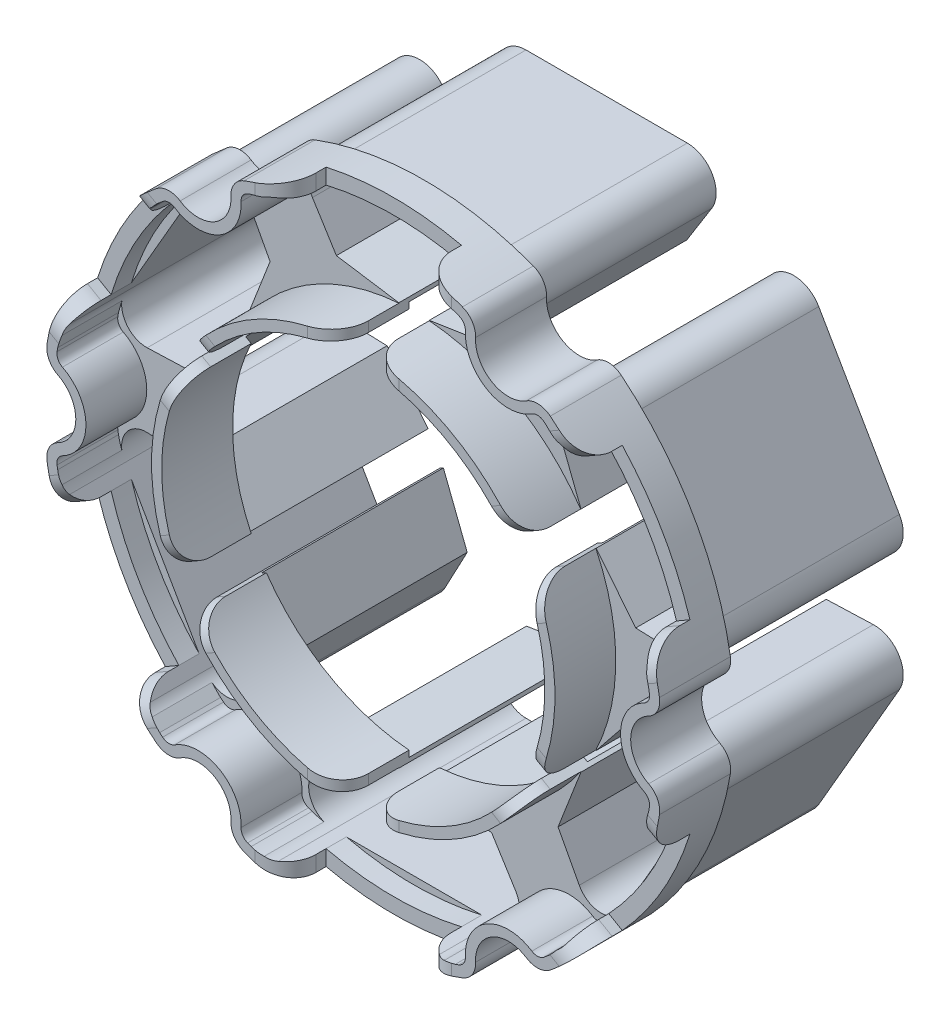
SolidWorks part; units mm, degrees
ref_plane "Ön Düzlem" through (0, 0, 0) normal (0, 0, 1) x (1, 0, 0)
ref_plane "Üst Düzlem" through (0, 0, 0) normal (0, 1, 0) x (1, 0, 0)
ref_plane "Sağ Düzlem" through (0, 0, 0) normal (1, 0, 0) x (0, 0, -1)
sketch "Çizim2" plane through (0, 0, 0) normal (0, 0, 1) x (1, 0, 0)
  line L0 (-1.5, 18.3137) -> (-1.5, 19.3137) construction
  line L13 (1.5, 18.3137) -> (1.5, 19.3137) construction
  line L14 (1.5, 19.3137) -> (8, 20.3137) construction
  line L15 (-1.5, 19.3137) -> (-8, 20.3137) construction
  line L16 (8, 20.3137) -> (10.5, 24.3137) construction
  line L17 (-8, 20.3137) -> (-10.5, 24.3137) construction
  line L18 (-7.956, 28.9037) -> (7.956, 28.9037) construction
  line L20 (-1.5, 19.4654) -> (-7.9092, 20.4515)
  line L21 (-7.9092, 20.4515) -> (-10.3728, 24.3932)
  line L22 (-7.956, 28.7537) -> (7.956, 28.7537)
  line L23 (7.9092, 20.4515) -> (10.3728, 24.3932)
  line L24 (1.5, 19.4654) -> (7.9092, 20.4515)
  line L27 (1.5, 19.8803) -> (7.6612, 20.8281)
  line L28 (7.6612, 20.8281) -> (10.0251, 24.6105)
  line L29 (-7.956, 28.3437) -> (7.956, 28.3437)
  line L30 (-7.6612, 20.8281) -> (-10.0251, 24.6105)
  line L31 (-1.5, 19.8803) -> (-7.6612, 20.8281)
  line L120 (-0.94, 18.3137) -> (-0.94, 19.7941) construction
  line L121 (-1.35, 18.3137) -> (-1.35, 19.4424) construction
  line L122 (1.35, 18.3137) -> (1.35, 19.4424) construction
  line L123 (0.94, 18.3137) -> (0.94, 19.7941) construction
  line L133 (-0.94, 19.7941) -> (-7.6612, 20.8281) construction
  line L134 (0.94, 19.7941) -> (7.6612, 20.8281) construction
  line L145 (-1.5, 19.8803) -> (-1.5, 19.4654)
  line L146 (1.5, 19.8803) -> (1.5, 19.4654)
  line L147 (17.8718, 8.7595) -> (21.8683, 3.7793) [skipped]
  line L148 (21.8683, 3.7793) -> (26.3259, 3.6232) [skipped]
  line L149 (20.5683, 21.0619) -> (28.5243, 7.2817) [skipped]
  line L150 (14.2071, 17.0488) -> (16.3007, 20.9872) [skipped]
  line L151 (16.5218, 11.0977) -> (14.2071, 17.0488) [skipped]
  line L152 (-1.35, 19.4424) -> (-7.9092, 20.4515) construction
  line L153 (16.1626, 10.8903) -> (13.7569, 17.0753) [skipped]
  line L154 (13.7569, 17.0753) -> (15.9387, 21.1797) [skipped]
  line L155 (20.9234, 21.2669) -> (28.8794, 7.4867) [skipped]
  line L156 (21.6661, 3.3761) -> (26.3115, 3.2135) [skipped]
  line L157 (17.5126, 8.552) -> (21.6661, 3.3761) [skipped]
  line L158 (1.35, 19.4424) -> (7.9092, 20.4515) construction
  line L159 (-17.8718, 8.7595) -> (-21.8683, 3.7793) [skipped]
  line L160 (-21.8683, 3.7793) -> (-26.3259, 3.6232) [skipped]
  line L161 (-28.5243, 7.2817) -> (-20.5683, 21.0619) [skipped]
  line L162 (-14.2071, 17.0488) -> (-16.3007, 20.9872) [skipped]
  line L163 (-16.5218, 11.0977) -> (-14.2071, 17.0488) [skipped]
  line L164 (16.4668, 11.2392) -> (14.2071, 17.0488)
  line L165 (-16.1626, 10.8903) -> (-13.7569, 17.0753) [skipped]
  line L166 (-13.7569, 17.0753) -> (-15.9387, 21.1797) [skipped]
  line L167 (-28.8794, 7.4867) -> (-20.9234, 21.2669) [skipped]
  line L168 (-21.6661, 3.3761) -> (-26.3115, 3.2135) [skipped]
  line L169 (-17.5126, 8.552) -> (-21.6661, 3.3761) [skipped]
  line L170 (14.2071, 17.0488) -> (16.3007, 20.9872)
  line L171 (17.5126, -8.552) -> (21.6661, -3.3761) [skipped]
  line L172 (21.6661, -3.3761) -> (26.3115, -3.2135) [skipped]
  line L173 (28.8794, -7.4867) -> (20.9234, -21.2669) [skipped]
  line L174 (13.7569, -17.0753) -> (15.9387, -21.1797) [skipped]
  line L175 (16.1626, -10.8903) -> (13.7569, -17.0753) [skipped]
  line L176 (20.5683, 21.0619) -> (28.5243, 7.2817)
  line L177 (16.5218, -11.0977) -> (14.2071, -17.0488) [skipped]
  line L178 (14.2071, -17.0488) -> (16.3007, -20.9872) [skipped]
  line L179 (28.5243, -7.2817) -> (20.5683, -21.0619) [skipped]
  line L180 (21.8683, -3.7793) -> (26.3259, -3.6232) [skipped]
  line L181 (17.8718, -8.7595) -> (21.8683, -3.7793) [skipped]
  line L182 (21.8683, 3.7793) -> (26.3259, 3.6232)
  line L183 (1.35, -19.4424) -> (7.9092, -20.4515) [skipped]
  line L184 (7.9092, -20.4515) -> (10.3728, -24.3932) [skipped]
  line L185 (7.956, -28.7537) -> (-7.956, -28.7537) [skipped]
  line L186 (-7.9092, -20.4515) -> (-10.3728, -24.3932) [skipped]
  line L187 (-1.35, -19.4424) -> (-7.9092, -20.4515) [skipped]
  line L188 (17.9668, 8.6411) -> (21.8683, 3.7793)
  line L189 (-1.35, -19.8572) -> (-7.6612, -20.8281) [skipped]
  line L190 (-7.6612, -20.8281) -> (-10.0251, -24.6105) [skipped]
  line L191 (7.956, -28.3437) -> (-7.956, -28.3437) [skipped]
  line L192 (7.6612, -20.8281) -> (10.0251, -24.6105) [skipped]
  line L193 (1.35, -19.8572) -> (7.6612, -20.8281) [skipped]
  line L194 (17.9668, 8.6411) -> (17.6076, 8.4337)
  line L195 (-16.1626, -10.8903) -> (-13.7569, -17.0753) [skipped]
  line L196 (-13.7569, -17.0753) -> (-15.9387, -21.1797) [skipped]
  line L197 (-20.9234, -21.2669) -> (-28.8794, -7.4867) [skipped]
  line L198 (-21.6661, -3.3761) -> (-26.3115, -3.2135) [skipped]
  line L199 (-17.5126, -8.552) -> (-21.6661, -3.3761) [skipped]
  line L200 (17.6076, 8.4337) -> (21.6661, 3.3761)
  line L201 (-17.8718, -8.7595) -> (-21.8683, -3.7793) [skipped]
  line L202 (-21.8683, -3.7793) -> (-26.3259, -3.6232) [skipped]
  line L203 (-20.5683, -21.0619) -> (-28.5243, -7.2817) [skipped]
  line L204 (-14.2071, -17.0488) -> (-16.3007, -20.9872) [skipped]
  line L205 (-16.5218, -11.0977) -> (-14.2071, -17.0488) [skipped]
  line L206 (21.6661, 3.3761) -> (26.3115, 3.2135)
  line L207 (20.9234, 21.2669) -> (28.8794, 7.4867)
  line L208 (13.7569, 17.0753) -> (15.9387, 21.1797)
  line L209 (16.1076, 11.0318) -> (13.7569, 17.0753)
  line L210 (16.4668, 11.2392) -> (16.1076, 11.0318)
  line L211 (17.9668, -8.6411) -> (21.8683, -3.7793)
  line L212 (21.8683, -3.7793) -> (26.3259, -3.6232)
  line L213 (28.5243, -7.2817) -> (20.5683, -21.0619)
  line L214 (14.2071, -17.0488) -> (16.3007, -20.9872)
  line L215 (16.4668, -11.2392) -> (14.2071, -17.0488)
  line L216 (16.4668, -11.2392) -> (16.1076, -11.0318)
  line L217 (16.1076, -11.0318) -> (13.7569, -17.0753)
  line L218 (13.7569, -17.0753) -> (15.9387, -21.1797)
  line L219 (28.8794, -7.4867) -> (20.9234, -21.2669)
  line L220 (21.6661, -3.3761) -> (26.3115, -3.2135)
  line L221 (17.6076, -8.4337) -> (21.6661, -3.3761)
  line L222 (17.9668, -8.6411) -> (17.6076, -8.4337)
  line L223 (1.5, -19.8803) -> (7.6612, -20.8281)
  line L224 (7.6612, -20.8281) -> (10.0251, -24.6105)
  line L225 (7.956, -28.3437) -> (-7.956, -28.3437)
  line L226 (-7.6612, -20.8281) -> (-10.0251, -24.6105)
  line L227 (-1.5, -19.8803) -> (-7.6612, -20.8281)
  line L228 (-1.5, -19.8803) -> (-1.5, -19.4654)
  line L229 (-1.5, -19.4654) -> (-7.9092, -20.4515)
  line L230 (-7.9092, -20.4515) -> (-10.3728, -24.3932)
  line L231 (7.956, -28.7537) -> (-7.956, -28.7537)
  line L232 (7.9092, -20.4515) -> (10.3728, -24.3932)
  line L233 (1.5, -19.4654) -> (7.9092, -20.4515)
  line L234 (1.5, -19.8803) -> (1.5, -19.4654)
  line L235 (-16.4668, -11.2392) -> (-14.2071, -17.0488)
  line L236 (-14.2071, -17.0488) -> (-16.3007, -20.9872)
  line L237 (-20.5683, -21.0619) -> (-28.5243, -7.2817)
  line L238 (-21.8683, -3.7793) -> (-26.3259, -3.6232)
  line L239 (-17.9668, -8.6411) -> (-21.8683, -3.7793)
  line L240 (-17.9668, -8.6411) -> (-17.6076, -8.4337)
  line L241 (-17.6076, -8.4337) -> (-21.6661, -3.3761)
  line L242 (-21.6661, -3.3761) -> (-26.3115, -3.2135)
  line L243 (-20.9234, -21.2669) -> (-28.8794, -7.4867)
  line L244 (-13.7569, -17.0753) -> (-15.9387, -21.1797)
  line L245 (-16.1076, -11.0318) -> (-13.7569, -17.0753)
  line L246 (-16.4668, -11.2392) -> (-16.1076, -11.0318)
  line L247 (-17.9668, 8.6411) -> (-21.8683, 3.7793)
  line L248 (-21.8683, 3.7793) -> (-26.3259, 3.6232)
  line L249 (-28.5243, 7.2817) -> (-20.5683, 21.0619)
  line L250 (-14.2071, 17.0488) -> (-16.3007, 20.9872)
  line L251 (-16.4668, 11.2392) -> (-14.2071, 17.0488)
  line L252 (-16.4668, 11.2392) -> (-16.1076, 11.0318)
  line L253 (-16.1076, 11.0318) -> (-13.7569, 17.0753)
  line L254 (-13.7569, 17.0753) -> (-15.9387, 21.1797)
  line L255 (-28.8794, 7.4867) -> (-20.9234, 21.2669)
  line L256 (-21.6661, 3.3761) -> (-26.3115, 3.2135)
  line L257 (-17.6076, 8.4337) -> (-21.6661, 3.3761)
  line L258 (-17.9668, 8.6411) -> (-17.6076, 8.4337)
  circle A0 centre (0, 0) radius 30.62 construction
  arc A1 (-7.956, 28.9037) -> (-10.5, 24.3137) centre (-7.956, 25.9037) ccw construction
  arc A2 (10.5, 24.3137) -> (7.956, 28.9037) centre (7.956, 25.9037) ccw construction
  circle A3 centre (-15.3101, 26.5179) radius 4.3797 construction
  circle A4 centre (-15.3101, 26.5179) radius 1.5 construction
  arc A5 (-7.956, 28.7537) -> (-10.3728, 24.3932) centre (-7.956, 25.9037) ccw
  arc A6 (10.3728, 24.3932) -> (7.956, 28.7537) centre (7.956, 25.9037) ccw
  arc A7 (10.0251, 24.6105) -> (7.956, 28.3437) centre (7.956, 25.9037) ccw
  arc A8 (-7.956, 28.3437) -> (-10.0251, 24.6105) centre (-7.956, 25.9037) ccw
  circle A9 centre (15.3101, 26.5179) radius 1.5 construction
  circle A14 centre (30.6203, 0) radius 1.5 construction
  circle A19 centre (15.3101, -26.5179) radius 1.5 construction
  circle A24 centre (-15.3101, -26.5179) radius 1.5 construction
  circle A29 centre (-30.6203, 0) radius 1.5 construction
  arc A34 (26.3259, 3.6232) -> (28.5243, 7.2817) centre (26.4112, 6.0617) ccw [skipped]
  arc A35 (20.5683, 21.0619) -> (16.3007, 20.9872) centre (18.4552, 19.8419) ccw [skipped]
  arc A36 (20.9234, 21.2669) -> (15.9387, 21.1797) centre (18.4552, 19.8419) ccw [skipped]
  arc A37 (26.3115, 3.2135) -> (28.8794, 7.4867) centre (26.4112, 6.0617) ccw [skipped]
  arc A38 (-28.5243, 7.2817) -> (-26.3259, 3.6232) centre (-26.4112, 6.0617) ccw [skipped]
  arc A39 (-16.3007, 20.9872) -> (-20.5683, 21.0619) centre (-18.4552, 19.8419) ccw [skipped]
  arc A40 (-15.9387, 21.1797) -> (-20.9234, 21.2669) centre (-18.4552, 19.8419) ccw [skipped]
  arc A41 (-28.8794, 7.4867) -> (-26.3115, 3.2135) centre (-26.4112, 6.0617) ccw [skipped]
  arc A42 (28.8794, -7.4867) -> (26.3115, -3.2135) centre (26.4112, -6.0617) ccw [skipped]
  arc A43 (15.9387, -21.1797) -> (20.9234, -21.2669) centre (18.4552, -19.8419) ccw [skipped]
  arc A44 (16.3007, -20.9872) -> (20.5683, -21.0619) centre (18.4552, -19.8419) ccw [skipped]
  arc A45 (28.5243, -7.2817) -> (26.3259, -3.6232) centre (26.4112, -6.0617) ccw [skipped]
  arc A46 (7.956, -28.7537) -> (10.3728, -24.3932) centre (7.956, -25.9037) ccw [skipped]
  arc A47 (-10.3728, -24.3932) -> (-7.956, -28.7537) centre (-7.956, -25.9037) ccw [skipped]
  arc A48 (-10.0251, -24.6105) -> (-7.956, -28.3437) centre (-7.956, -25.9037) ccw [skipped]
  arc A49 (7.956, -28.3437) -> (10.0251, -24.6105) centre (7.956, -25.9037) ccw [skipped]
  arc A50 (-20.9234, -21.2669) -> (-15.9387, -21.1797) centre (-18.4552, -19.8419) ccw [skipped]
  arc A51 (-26.3115, -3.2135) -> (-28.8794, -7.4867) centre (-26.4112, -6.0617) ccw [skipped]
  arc A52 (-26.3259, -3.6232) -> (-28.5243, -7.2817) centre (-26.4112, -6.0617) ccw [skipped]
  arc A53 (-20.5683, -21.0619) -> (-16.3007, -20.9872) centre (-18.4552, -19.8419) ccw [skipped]
  arc A54 (20.5683, 21.0619) -> (16.3007, 20.9872) centre (18.4552, 19.8419) ccw
  arc A55 (26.3259, 3.6232) -> (28.5243, 7.2817) centre (26.4112, 6.0617) ccw
  arc A56 (26.3115, 3.2135) -> (28.8794, 7.4867) centre (26.4112, 6.0617) ccw
  arc A57 (20.9234, 21.2669) -> (15.9387, 21.1797) centre (18.4552, 19.8419) ccw
  arc A58 (28.5243, -7.2817) -> (26.3259, -3.6232) centre (26.4112, -6.0617) ccw
  arc A59 (16.3007, -20.9872) -> (20.5683, -21.0619) centre (18.4552, -19.8419) ccw
  arc A60 (15.9387, -21.1797) -> (20.9234, -21.2669) centre (18.4552, -19.8419) ccw
  arc A61 (28.8794, -7.4867) -> (26.3115, -3.2135) centre (26.4112, -6.0617) ccw
  arc A62 (7.956, -28.3437) -> (10.0251, -24.6105) centre (7.956, -25.9037) ccw
  arc A63 (-10.0251, -24.6105) -> (-7.956, -28.3437) centre (-7.956, -25.9037) ccw
  arc A64 (-10.3728, -24.3932) -> (-7.956, -28.7537) centre (-7.956, -25.9037) ccw
  arc A65 (7.956, -28.7537) -> (10.3728, -24.3932) centre (7.956, -25.9037) ccw
  arc A66 (-20.5683, -21.0619) -> (-16.3007, -20.9872) centre (-18.4552, -19.8419) ccw
  arc A67 (-26.3259, -3.6232) -> (-28.5243, -7.2817) centre (-26.4112, -6.0617) ccw
  arc A68 (-26.3115, -3.2135) -> (-28.8794, -7.4867) centre (-26.4112, -6.0617) ccw
  arc A69 (-20.9234, -21.2669) -> (-15.9387, -21.1797) centre (-18.4552, -19.8419) ccw
  arc A70 (-28.5243, 7.2817) -> (-26.3259, 3.6232) centre (-26.4112, 6.0617) ccw
  arc A71 (-16.3007, 20.9872) -> (-20.5683, 21.0619) centre (-18.4552, 19.8419) ccw
  arc A72 (-15.9387, 21.1797) -> (-20.9234, 21.2669) centre (-18.4552, 19.8419) ccw
  arc A73 (-28.8794, 7.4867) -> (-26.3115, 3.2135) centre (-26.4112, 6.0617) ccw
  point P159 (0, 0)
  point P176 (0, 0)
  point P189 (0, 0)
  dimension "D1" = 61.24
  dimension "D8" = 3
  dimension "D9" = 3
  dimension "D10" = 3
  dimension "D11" = 7.3541
  dimension "D12" = 4.8101
  dimension "D14" = 15.912
  dimension "D2" = 4
  dimension "D3" = 4
  dimension "D4" = 6.5
  dimension "D5" = 6.5
  dimension "D6" = 1
  dimension "D7" = 1
  dimension "D13" = 2.2043
  dimension "D15" = 3
  dimension "D16" = 1
  dimension "D17" = 1
  dimension "D18" = 21
  dimension "D19" = 1.5
  dimension "D20" = 18.375
  dimension "D24" = 6
  dimension "D25" = 3
  dimension "D26" = 1.5
  dimension "D21" = 0.15
  dimension "D22" = 0.41
  dimension "D23" = 6
extrude "Yükseklik-Ekstrüzyon1" add sketch "Çizim2" along normal blind 18
sketch "Çizim3" plane through (0, 0, 18) normal (0, 0, 1) x (1, 0, 0)
  line L71 (10.0251, 24.6105) -> (7.6612, 20.8281) construction
  line L72 (7.6612, 20.8281) -> (1.5, 19.8803) construction
  line L73 (-7.956, 28.3437) -> (7.956, 28.3437) construction
  line L74 (-1.5, 19.8803) -> (-7.6612, 20.8281) construction
  line L75 (-7.6612, 20.8281) -> (-10.0251, 24.6105) construction
  line L76 (10.0251, 24.6105) -> (7.6612, 20.8281)
  line L77 (7.6612, 20.8281) -> (1.5, 19.8803)
  line L78 (-7.956, 28.3437) -> (7.956, 28.3437)
  line L79 (-1.5, 19.8803) -> (-7.6612, 20.8281)
  line L80 (-7.6612, 20.8281) -> (-10.0251, 24.6105)
  line L81 (-1.5, 19.8803) -> (-1.5, 18.8404)
  line L82 (1.5, 19.8803) -> (1.5, 18.8404)
  line L83 (17.9668, 8.6411) -> (17.0662, 8.1212)
  line L84 (21.8683, 3.7793) -> (17.9668, 8.6411)
  line L85 (26.3259, 3.6232) -> (21.8683, 3.7793)
  line L86 (20.5683, 21.0619) -> (28.5243, 7.2817)
  line L87 (14.2071, 17.0488) -> (16.3007, 20.9872)
  line L88 (16.4668, 11.2392) -> (14.2071, 17.0488)
  line L89 (16.4668, 11.2392) -> (15.5662, 10.7192)
  line L90 (16.4668, -11.2392) -> (15.5662, -10.7192)
  line L91 (14.2071, -17.0488) -> (16.4668, -11.2392)
  line L92 (16.3007, -20.9872) -> (14.2071, -17.0488)
  line L93 (28.5243, -7.2817) -> (20.5683, -21.0619)
  line L94 (21.8683, -3.7793) -> (26.3259, -3.6232)
  line L95 (17.9668, -8.6411) -> (21.8683, -3.7793)
  line L96 (17.9668, -8.6411) -> (17.0662, -8.1212)
  line L97 (-1.5, -19.8803) -> (-1.5, -18.8404)
  line L98 (-7.6612, -20.8281) -> (-1.5, -19.8803)
  line L99 (-10.0251, -24.6105) -> (-7.6612, -20.8281)
  line L100 (7.956, -28.3437) -> (-7.956, -28.3437)
  line L101 (7.6612, -20.8281) -> (10.0251, -24.6105)
  line L102 (1.5, -19.8803) -> (7.6612, -20.8281)
  line L103 (1.5, -19.8803) -> (1.5, -18.8404)
  line L104 (-17.9668, -8.6411) -> (-17.0662, -8.1212)
  line L105 (-21.8683, -3.7793) -> (-17.9668, -8.6411)
  line L106 (-26.3259, -3.6232) -> (-21.8683, -3.7793)
  line L107 (-20.5683, -21.0619) -> (-28.5243, -7.2817)
  line L108 (-14.2071, -17.0488) -> (-16.3007, -20.9872)
  line L109 (-16.4668, -11.2392) -> (-14.2071, -17.0488)
  line L110 (-16.4668, -11.2392) -> (-15.5662, -10.7192)
  line L111 (-16.4668, 11.2392) -> (-15.5662, 10.7192)
  line L112 (-14.2071, 17.0488) -> (-16.4668, 11.2392)
  line L113 (-16.3007, 20.9872) -> (-14.2071, 17.0488)
  line L114 (-28.5243, 7.2817) -> (-20.5683, 21.0619)
  line L115 (-21.8683, 3.7793) -> (-26.3259, 3.6232)
  line L116 (-17.9668, 8.6411) -> (-21.8683, 3.7793)
  line L117 (-17.9668, 8.6411) -> (-17.0662, 8.1212)
  arc A0 (-18.0344, 24.7456) -> (-30.4475, 3.2454) centre (0, 0) ccw
  circle A1 centre (-15.31, 26.5177) radius 4.5296 construction
  arc A3 (-7.956, 28.7537) -> (-10.3728, 24.3932) centre (-7.956, 25.9037) ccw construction
  arc A4 (-18.0344, 24.7456) -> (-12.4131, 27.991) centre (-15.31, 26.5177) ccw
  arc A5 (12.4131, 27.991) -> (18.0344, 24.7456) centre (15.31, 26.5177) ccw
  arc A6 (30.4475, 3.2454) -> (30.4475, -3.2454) centre (30.62, 0) ccw
  arc A7 (18.0344, -24.7456) -> (12.4131, -27.991) centre (15.31, -26.5177) ccw
  arc A8 (-12.4131, -27.991) -> (-18.0344, -24.7456) centre (-15.31, -26.5177) ccw
  arc A9 (-30.4475, -3.2454) -> (-30.4475, 3.2454) centre (-30.62, 0) ccw
  arc A10 (12.4131, 27.991) -> (-12.4131, 27.991) centre (0, 0) ccw
  arc A11 (30.4475, 3.2454) -> (18.0344, 24.7456) centre (0, 0) ccw
  arc A12 (18.0344, -24.7456) -> (30.4475, -3.2454) centre (0, 0) ccw
  arc A13 (-12.4131, -27.991) -> (12.4131, -27.991) centre (0, 0) ccw
  arc A14 (-30.4475, -3.2454) -> (-18.0344, -24.7456) centre (0, 0) ccw
  arc A35 (-1.5, 18.8404) -> (-15.5662, 10.7192) centre (0, 0) ccw
  arc A36 (10.0251, 24.6105) -> (7.956, 28.3437) centre (7.956, 25.9037) ccw construction
  arc A37 (-7.956, 28.3437) -> (-10.0251, 24.6105) centre (-7.956, 25.9037) ccw construction
  arc A38 (10.0251, 24.6105) -> (7.956, 28.3437) centre (7.956, 25.9037) ccw
  arc A39 (-7.956, 28.3437) -> (-10.0251, 24.6105) centre (-7.956, 25.9037) ccw
  arc A40 (26.3259, 3.6232) -> (28.5243, 7.2817) centre (26.4112, 6.0617) ccw
  arc A41 (20.5683, 21.0619) -> (16.3007, 20.9872) centre (18.4552, 19.8419) ccw
  arc A42 (16.3007, -20.9872) -> (20.5683, -21.0619) centre (18.4552, -19.8419) ccw
  arc A43 (28.5243, -7.2817) -> (26.3259, -3.6232) centre (26.4112, -6.0617) ccw
  arc A44 (-10.0251, -24.6105) -> (-7.956, -28.3437) centre (-7.956, -25.9037) ccw
  arc A45 (7.956, -28.3437) -> (10.0251, -24.6105) centre (7.956, -25.9037) ccw
  arc A46 (-26.3259, -3.6232) -> (-28.5243, -7.2817) centre (-26.4112, -6.0617) ccw
  arc A47 (-20.5683, -21.0619) -> (-16.3007, -20.9872) centre (-18.4552, -19.8419) ccw
  arc A48 (-16.3007, 20.9872) -> (-20.5683, 21.0619) centre (-18.4552, 19.8419) ccw
  arc A49 (-28.5243, 7.2817) -> (-26.3259, 3.6232) centre (-26.4112, 6.0617) ccw
  arc A50 (15.5662, 10.7192) -> (1.5, 18.8404) centre (0, 0) ccw
  arc A51 (17.0662, -8.1212) -> (17.0662, 8.1212) centre (0, 0) ccw
  arc A52 (1.5, -18.8404) -> (15.5662, -10.7192) centre (0, 0) ccw
  arc A53 (-15.5662, -10.7192) -> (-1.5, -18.8404) centre (0, 0) ccw
  arc A54 (-17.0662, 8.1212) -> (-17.0662, -8.1212) centre (0, 0) ccw
  arc A55 (-15.9387, 21.1797) -> (-20.9234, 21.2669) centre (-18.4552, 19.8419) ccw construction
  point P30 (0, 0)
  point P102 (0, 0)
  point P103 (0, 0)
  point P141 (0, 0)
  dimension "D1" = 61.24
  dimension "D2" = 6.5
  dimension "D4" = 37.8
  dimension "D3" = 6
  dimension "D5" = 6
extrude "Yükseklik-Ekstrüzyon2" add sketch "Çizim3" along normal blind 1
fillet "Radyus2" radius 2 12 edges at (18.0344, 24.7456, 18.5) (12.4131, 27.991, 18.5) (30.4475, 3.2454, 18.5) (30.4475, -3.2454, 18.5) (12.4131, -27.991, 18.5) (18.0344, -24.7456, 18.5) (-12.4131, -27.991, 18.5) (-18.0344, -24.7456, 18.5) (-30.4475, -3.2454, 18.5) (-30.4475, 3.2454, 18.5) (-12.4131, 27.991, 18.5) (-18.0344, 24.7456, 18.5)
sketch "Çizim4" plane through (0, 0, 19) normal (0, 0, 1) x (1, 0, 0)
  line L0 (-1.5, 18.8404) -> (-1.5, 19.8434)
  line L1 (-1.5, 19.8803) -> (-1.5, 18.8404) construction
  line L2 (1.5, 18.8404) -> (1.5, 19.8434)
  line L3 (1.5, 18.8404) -> (1.5, 19.8803) construction
  line L4 (15.5662, 10.7192) -> (16.4349, 11.2207)
  line L5 (17.0662, 8.1212) -> (17.9349, 8.6227)
  line L6 (17.0662, -8.1212) -> (17.9349, -8.6227)
  line L7 (15.5662, -10.7192) -> (16.4349, -11.2207)
  line L8 (1.5, -18.8404) -> (1.5, -19.8434)
  line L9 (-1.5, -18.8404) -> (-1.5, -19.8434)
  line L10 (-15.5662, -10.7192) -> (-16.4349, -11.2207)
  line L11 (-17.0662, -8.1212) -> (-17.9349, -8.6227)
  line L12 (-17.0662, 8.1212) -> (-17.9349, 8.6227)
  line L13 (-15.5662, 10.7192) -> (-16.4349, 11.2207)
  arc A0 (-15.5662, -10.7192) -> (-1.5, -18.8404) centre (0, 0) ccw construction
  arc A1 (1.5, -18.8404) -> (15.5662, -10.7192) centre (0, 0) ccw construction
  arc A2 (17.0662, -8.1212) -> (17.0662, 8.1212) centre (0, 0) ccw construction
  arc A3 (15.5662, 10.7192) -> (1.5, 18.8404) centre (0, 0) ccw construction
  arc A4 (-1.5, 18.8404) -> (-15.5662, 10.7192) centre (0, 0) ccw construction
  arc A5 (-17.0662, 8.1212) -> (-17.0662, -8.1212) centre (0, 0) ccw construction
  arc A6 (-15.5662, -10.7192) -> (-1.5, -18.8404) centre (0, 0) ccw
  arc A7 (1.5, -18.8404) -> (15.5662, -10.7192) centre (0, 0) ccw
  arc A8 (17.0662, -8.1212) -> (17.0662, 8.1212) centre (0, 0) ccw
  arc A9 (15.5662, 10.7192) -> (1.5, 18.8404) centre (0, 0) ccw
  arc A10 (-1.5, 18.8404) -> (-15.5662, 10.7192) centre (0, 0) ccw
  arc A11 (-17.0662, 8.1212) -> (-17.0662, -8.1212) centre (0, 0) ccw
  arc A12 (-17.9349, 8.6227) -> (-17.9349, -8.6227) centre (0, 0) ccw
  arc A13 (-1.5, 19.8434) -> (-16.4349, 11.2207) centre (0, 0) ccw
  arc A14 (16.4349, 11.2207) -> (1.5, 19.8434) centre (0, 0) ccw
  arc A15 (17.9349, -8.6227) -> (17.9349, 8.6227) centre (0, 0) ccw
  arc A16 (1.5, -19.8434) -> (16.4349, -11.2207) centre (0, 0) ccw
  arc A17 (-16.4349, -11.2207) -> (-1.5, -19.8434) centre (0, 0) ccw
  point P47 (0, 0)
  dimension "D1" = 1
  dimension "D2" = 6
extrude "Yükseklik-Ekstrüzyon3" add sketch "Çizim4" along normal blind 6
fillet "Radyus3" radius 3 12 edges at (-16.0006, -10.97, 25) (-1.5, -19.3419, 25) (1.5, -19.3419, 25) (16.0006, -10.97, 25) (17.5006, 8.3719, 25) (17.5006, -8.3719, 25) (16.0006, 10.97, 25) (1.5, 19.3419, 25) (-1.5, 19.3419, 25) (-16.0006, 10.97, 25) (-17.5006, 8.3719, 25) (-17.5006, -8.3719, 25)
sketch "Çizim5" plane through (0, 0, 19) normal (0, 0, 1) x (1, 0, 0)
  line L0 (-28.5243, -7.2817) -> (-20.5683, -21.0619) construction
  line L1 (-7.956, -28.3437) -> (7.956, -28.3437) construction
  line L2 (20.5683, -21.0619) -> (28.5243, -7.2817) construction
  line L3 (28.5243, 7.2817) -> (20.5683, 21.0619) construction
  line L4 (-20.5683, 21.0619) -> (-28.5243, 7.2817) construction
  line L5 (-28.5243, -7.2817) -> (-27.8859, -8.3875)
  line L6 (-7.956, -28.3437) -> (-6.6791, -28.3437)
  line L7 (20.5683, -21.0619) -> (21.2068, -19.9561)
  line L8 (28.5243, 7.2817) -> (27.8859, 8.3875)
  line L9 (-20.5683, 21.0619) -> (-21.2068, 19.9561)
  line L10 (-27.8859, 8.3875) -> (-28.5243, 7.2817)
  line L11 (-21.2068, -19.9561) -> (-20.5683, -21.0619)
  line L12 (6.6791, -28.3437) -> (7.956, -28.3437)
  line L13 (27.8859, -8.3875) -> (28.5243, -7.2817)
  line L14 (21.2068, 19.9561) -> (20.5683, 21.0619)
  line L15 (7.956, 28.3437) -> (-7.956, 28.3437) construction
  line L16 (7.956, 28.3437) -> (6.6791, 28.3437)
  line L17 (-6.6791, 28.3437) -> (-7.956, 28.3437)
  arc A0 (28.7285, 4.7588) -> (28.6651, 5.127) centre (0, 0) ccw
  arc A1 (18.4855, 22.5002) -> (17.8959, 22.5333) centre (18.1681, 22.1139) ccw
  arc A2 (10.5664, 26.765) -> (17.8959, 22.5333) centre (15.31, 26.5177) ccw
  arc A3 (10.5664, 26.765) -> (10.243, 27.259) centre (10.0671, 26.791) ccw
  arc A4 (10.243, 27.259) -> (9.8924, 27.3882) centre (0, 0) ccw
  arc A5 (-10.243, 27.259) -> (-10.5664, 26.765) centre (-10.0671, 26.791) ccw
  arc A6 (-17.8959, 22.5333) -> (-10.5664, 26.765) centre (-15.31, 26.5177) ccw
  arc A7 (-17.8959, 22.5333) -> (-18.4855, 22.5002) centre (-18.1681, 22.1139) ccw
  arc A8 (-18.4855, 22.5002) -> (-18.7727, 22.2612) centre (0, 0) ccw
  arc A9 (-28.7285, 4.7588) -> (-28.4624, 4.2317) centre (-28.2352, 4.6771) ccw
  arc A10 (-28.4624, -4.2317) -> (-28.4624, 4.2317) centre (-30.62, 0) ccw
  arc A11 (-28.4624, -4.2317) -> (-28.7285, -4.7588) centre (-28.2352, -4.6771) ccw
  arc A12 (-28.7285, -4.7588) -> (-28.6651, -5.127) centre (0, 0) ccw
  arc A13 (-18.4855, -22.5002) -> (-17.8959, -22.5333) centre (-18.1681, -22.1139) ccw
  arc A14 (-10.5664, -26.765) -> (-17.8959, -22.5333) centre (-15.31, -26.5177) ccw
  arc A15 (-10.5664, -26.765) -> (-10.243, -27.259) centre (-10.0671, -26.791) ccw
  arc A16 (-10.243, -27.259) -> (-9.8924, -27.3882) centre (0, 0) ccw
  arc A17 (10.243, -27.259) -> (10.5664, -26.765) centre (10.0671, -26.791) ccw
  arc A18 (17.8959, -22.5333) -> (10.5664, -26.765) centre (15.31, -26.5177) ccw
  arc A19 (17.8959, -22.5333) -> (18.4855, -22.5002) centre (18.1681, -22.1139) ccw
  arc A20 (18.4855, -22.5002) -> (18.7727, -22.2612) centre (0, 0) ccw
  arc A21 (28.7285, -4.7588) -> (28.4624, -4.2317) centre (28.2352, -4.6771) ccw
  arc A22 (28.4624, 4.2317) -> (28.4624, -4.2317) centre (30.62, 0) ccw
  arc A23 (28.4624, 4.2317) -> (28.7285, 4.7588) centre (28.2352, 4.6771) ccw
  arc A24 (30.2084, 5.004) -> (19.4377, 23.6592) centre (0, 0) ccw
  arc A25 (19.4377, 23.6592) -> (17.0793, 23.7915) centre (18.1681, 22.1139) ccw
  arc A26 (12.0644, 26.6869) -> (17.0793, 23.7915) centre (15.31, 26.5177) ccw
  arc A27 (12.0644, 26.6869) -> (10.7706, 28.6632) centre (10.0671, 26.791) ccw
  arc A28 (10.7706, 28.6632) -> (-10.7706, 28.6632) centre (0, 0) ccw
  arc A29 (-10.7706, 28.6632) -> (-12.0644, 26.6869) centre (-10.0671, 26.791) ccw
  arc A30 (-17.0793, 23.7915) -> (-12.0644, 26.6869) centre (-15.31, 26.5177) ccw
  arc A31 (-17.0793, 23.7915) -> (-19.4377, 23.6592) centre (-18.1681, 22.1139) ccw
  arc A32 (-19.4377, 23.6592) -> (-30.2084, 5.004) centre (0, 0) ccw
  arc A33 (-30.2084, 5.004) -> (-29.1437, 2.8954) centre (-28.2352, 4.6771) ccw
  arc A34 (-29.1437, -2.8954) -> (-29.1437, 2.8954) centre (-30.62, 0) ccw
  arc A35 (-29.1437, -2.8954) -> (-30.2084, -5.004) centre (-28.2352, -4.6771) ccw
  arc A36 (-30.2084, -5.004) -> (-19.4377, -23.6592) centre (0, 0) ccw
  arc A37 (-19.4377, -23.6592) -> (-17.0793, -23.7915) centre (-18.1681, -22.1139) ccw
  arc A38 (-12.0644, -26.6869) -> (-17.0793, -23.7915) centre (-15.31, -26.5177) ccw
  arc A39 (-12.0644, -26.6869) -> (-10.7706, -28.6632) centre (-10.0671, -26.791) ccw
  arc A40 (-10.7706, -28.6632) -> (10.7706, -28.6632) centre (0, 0) ccw
  arc A41 (10.7706, -28.6632) -> (12.0644, -26.6869) centre (10.0671, -26.791) ccw
  arc A42 (17.0793, -23.7915) -> (12.0644, -26.6869) centre (15.31, -26.5177) ccw
  arc A43 (17.0793, -23.7915) -> (19.4377, -23.6592) centre (18.1681, -22.1139) ccw
  arc A44 (19.4377, -23.6592) -> (30.2084, -5.004) centre (0, 0) ccw
  arc A45 (30.2084, -5.004) -> (29.1437, -2.8954) centre (28.2352, -4.6771) ccw
  arc A46 (29.1437, 2.8954) -> (29.1437, -2.8954) centre (30.62, 0) ccw
  arc A47 (29.1437, 2.8954) -> (30.2084, 5.004) centre (28.2352, 4.6771) ccw
  arc A48 (30.2084, 5.004) -> (19.4377, 23.6592) centre (0, 0) ccw
  arc A49 (19.4377, 23.6592) -> (17.0793, 23.7915) centre (18.1681, 22.1139) ccw
  arc A50 (12.0644, 26.6869) -> (17.0793, 23.7915) centre (15.31, 26.5177) ccw
  arc A51 (12.0644, 26.6869) -> (10.7706, 28.6632) centre (10.0671, 26.791) ccw
  arc A52 (10.7706, 28.6632) -> (-10.7706, 28.6632) centre (0, 0) ccw
  arc A53 (-10.7706, 28.6632) -> (-12.0644, 26.6869) centre (-10.0671, 26.791) ccw
  arc A54 (-17.0793, 23.7915) -> (-12.0644, 26.6869) centre (-15.31, 26.5177) ccw
  arc A55 (-17.0793, 23.7915) -> (-19.4377, 23.6592) centre (-18.1681, 22.1139) ccw
  arc A56 (-19.4377, 23.6592) -> (-30.2084, 5.004) centre (0, 0) ccw
  arc A57 (-30.2084, 5.004) -> (-29.1437, 2.8954) centre (-28.2352, 4.6771) ccw
  arc A58 (-29.1437, -2.8954) -> (-29.1437, 2.8954) centre (-30.62, 0) ccw
  arc A59 (-29.1437, -2.8954) -> (-30.2084, -5.004) centre (-28.2352, -4.6771) ccw
  arc A60 (-30.2084, -5.004) -> (-19.4377, -23.6592) centre (0, 0) ccw
  arc A61 (-19.4377, -23.6592) -> (-17.0793, -23.7915) centre (-18.1681, -22.1139) ccw
  arc A62 (-12.0644, -26.6869) -> (-17.0793, -23.7915) centre (-15.31, -26.5177) ccw
  arc A63 (-12.0644, -26.6869) -> (-10.7706, -28.6632) centre (-10.0671, -26.791) ccw
  arc A64 (-10.7706, -28.6632) -> (10.7706, -28.6632) centre (0, 0) ccw
  arc A65 (10.7706, -28.6632) -> (12.0644, -26.6869) centre (10.0671, -26.791) ccw
  arc A66 (17.0793, -23.7915) -> (12.0644, -26.6869) centre (15.31, -26.5177) ccw
  arc A67 (17.0793, -23.7915) -> (19.4377, -23.6592) centre (18.1681, -22.1139) ccw
  arc A68 (19.4377, -23.6592) -> (30.2084, -5.004) centre (0, 0) ccw
  arc A69 (30.2084, -5.004) -> (29.1437, -2.8954) centre (28.2352, -4.6771) ccw
  arc A70 (29.1437, 2.8954) -> (29.1437, -2.8954) centre (30.62, 0) ccw
  arc A71 (29.1437, 2.8954) -> (30.2084, 5.004) centre (28.2352, 4.6771) ccw
  arc A72 (-28.5243, 7.2817) -> (-26.3259, 3.6232) centre (-26.4112, 6.0617) ccw construction
  arc A73 (-26.3259, -3.6232) -> (-28.5243, -7.2817) centre (-26.4112, -6.0617) ccw construction
  arc A74 (-20.5683, -21.0619) -> (-16.3007, -20.9872) centre (-18.4552, -19.8419) ccw construction
  arc A75 (-10.0251, -24.6105) -> (-7.956, -28.3437) centre (-7.956, -25.9037) ccw construction
  arc A76 (7.956, -28.3437) -> (10.0251, -24.6105) centre (7.956, -25.9037) ccw construction
  arc A77 (16.3007, -20.9872) -> (20.5683, -21.0619) centre (18.4552, -19.8419) ccw construction
  arc A78 (28.5243, -7.2817) -> (26.3259, -3.6232) centre (26.4112, -6.0617) ccw construction
  arc A79 (26.3259, 3.6232) -> (28.5243, 7.2817) centre (26.4112, 6.0617) ccw construction
  arc A80 (20.5683, 21.0619) -> (16.3007, 20.9872) centre (18.4552, 19.8419) ccw construction
  arc A81 (10.0251, 24.6105) -> (7.956, 28.3437) centre (7.956, 25.9037) ccw construction
  arc A82 (-7.956, 28.3437) -> (-10.0251, 24.6105) centre (-7.956, 25.9037) ccw construction
  arc A83 (-16.3007, 20.9872) -> (-20.5683, 21.0619) centre (-18.4552, 19.8419) ccw construction
  arc A84 (-28.5243, 7.2817) -> (-28.6651, 5.127) centre (-26.4112, 6.0617) ccw
  arc A85 (-28.6651, -5.127) -> (-28.5243, -7.2817) centre (-26.4112, -6.0617) ccw
  arc A86 (-20.5683, -21.0619) -> (-18.7727, -22.2612) centre (-18.4552, -19.8419) ccw
  arc A87 (-9.8924, -27.3882) -> (-7.956, -28.3437) centre (-7.956, -25.9037) ccw
  arc A88 (7.956, -28.3437) -> (9.8924, -27.3882) centre (7.956, -25.9037) ccw
  arc A89 (18.7727, -22.2612) -> (20.5683, -21.0619) centre (18.4552, -19.8419) ccw
  arc A90 (28.5243, -7.2817) -> (28.6651, -5.127) centre (26.4112, -6.0617) ccw
  arc A91 (28.6651, 5.127) -> (28.5243, 7.2817) centre (26.4112, 6.0617) ccw
  arc A92 (20.5683, 21.0619) -> (18.7727, 22.2612) centre (18.4552, 19.8419) ccw
  arc A93 (9.8924, 27.3882) -> (7.956, 28.3437) centre (7.956, 25.9037) ccw
  arc A94 (-7.956, 28.3437) -> (-9.8924, 27.3882) centre (-7.956, 25.9037) ccw
  arc A95 (-18.7727, 22.2612) -> (-20.5683, 21.0619) centre (-18.4552, 19.8419) ccw
  arc A96 (-21.2068, 19.9561) -> (-27.8859, 8.3875) centre (0, 0) ccw
  arc A97 (-18.4855, 22.5002) -> (-28.7285, 4.7588) centre (0, 0) ccw construction
  arc A98 (-28.6651, 5.127) -> (-28.7285, 4.7588) centre (0, 0) ccw
  arc A99 (-27.8859, -8.3875) -> (-21.2068, -19.9561) centre (0, 0) ccw
  arc A100 (-28.7285, -4.7588) -> (-18.4855, -22.5002) centre (0, 0) ccw construction
  arc A101 (-18.7727, -22.2612) -> (-18.4855, -22.5002) centre (0, 0) ccw
  arc A102 (-6.6791, -28.3437) -> (6.6791, -28.3437) centre (0, 0) ccw
  arc A103 (-10.243, -27.259) -> (10.243, -27.259) centre (0, 0) ccw construction
  arc A104 (9.8924, -27.3882) -> (10.243, -27.259) centre (0, 0) ccw
  arc A105 (21.2068, -19.9561) -> (27.8859, -8.3875) centre (0, 0) ccw
  arc A106 (18.4855, -22.5002) -> (28.7285, -4.7588) centre (0, 0) ccw construction
  arc A107 (28.6651, -5.127) -> (28.7285, -4.7588) centre (0, 0) ccw
  arc A108 (27.8859, 8.3875) -> (21.2068, 19.9561) centre (0, 0) ccw
  arc A109 (28.7285, 4.7588) -> (18.4855, 22.5002) centre (0, 0) ccw construction
  arc A110 (18.7727, 22.2612) -> (18.4855, 22.5002) centre (0, 0) ccw
  arc A111 (6.6791, 28.3437) -> (-6.6791, 28.3437) centre (0, 0) ccw
  arc A112 (10.243, 27.259) -> (-10.243, 27.259) centre (0, 0) ccw construction
  arc A113 (-9.8924, 27.3882) -> (-10.243, 27.259) centre (0, 0) ccw
  dimension "D1" = 0
  dimension "D2" = 1.5
extrude "Yükseklik-Ekstrüzyon4" add sketch "Çizim5" along normal blind 6
sketch "Çizim6" plane through (0, 0, 25) normal (0, 0, 1) x (1, 0, 0)
  line L0 (-6.6791, 28.3437) -> (-6.6791, 29.8827)
  line L1 (6.6791, 28.3437) -> (6.6791, 29.8827)
  line L2 (21.2068, 19.9561) -> (22.5396, 20.7256)
  line L3 (27.8859, 8.3875) -> (29.2187, 9.157)
  line L4 (27.8859, -8.3875) -> (29.2187, -9.157)
  line L5 (21.2068, -19.9561) -> (22.5396, -20.7256)
  line L6 (6.6791, -28.3437) -> (6.6791, -29.8827)
  line L7 (-6.6791, -28.3437) -> (-6.6791, -29.8827)
  line L8 (-21.2068, -19.9561) -> (-22.5396, -20.7256)
  line L9 (-27.8859, -8.3875) -> (-29.2187, -9.157)
  line L10 (-27.8859, 8.3875) -> (-29.2187, 9.157)
  line L11 (-21.2068, 19.9561) -> (-22.5396, 20.7256)
  line L12 (6.6791, 28.3437) -> (-6.6791, 28.3437) construction
  line L13 (27.8859, 8.3875) -> (21.2068, 19.9561) construction
  line L14 (21.2068, -19.9561) -> (27.8859, -8.3875) construction
  line L15 (-6.6791, -28.3437) -> (6.6791, -28.3437) construction
  line L16 (-27.8859, -8.3875) -> (-21.2068, -19.9561) construction
  line L17 (-21.2068, 19.9561) -> (-27.8859, 8.3875) construction
  line L18 (-21.2068, 19.9561) -> (-27.8859, 8.3875)
  line L19 (-27.8859, -8.3875) -> (-21.2068, -19.9561)
  line L20 (-6.6791, -28.3437) -> (6.6791, -28.3437)
  line L21 (21.2068, -19.9561) -> (27.8859, -8.3875)
  line L22 (27.8859, 8.3875) -> (21.2068, 19.9561)
  line L23 (6.6791, 28.3437) -> (-6.6791, 28.3437)
  arc A24 (29.1437, 2.8954) -> (30.2084, 5.004) centre (28.2352, 4.6771) ccw
  arc A25 (30.2084, 5.004) -> (19.4377, 23.6592) centre (0, 0) ccw
  arc A26 (19.4377, 23.6592) -> (17.0793, 23.7915) centre (18.1681, 22.1139) ccw
  arc A27 (12.0644, 26.6869) -> (17.0793, 23.7915) centre (15.31, 26.5177) ccw
  arc A28 (12.0644, 26.6869) -> (10.7706, 28.6632) centre (10.0671, 26.791) ccw
  arc A29 (10.7706, 28.6632) -> (-10.7706, 28.6632) centre (0, 0) ccw
  arc A30 (-10.7706, 28.6632) -> (-12.0644, 26.6869) centre (-10.0671, 26.791) ccw
  arc A31 (-17.0793, 23.7915) -> (-12.0644, 26.6869) centre (-15.31, 26.5177) ccw
  arc A32 (-17.0793, 23.7915) -> (-19.4377, 23.6592) centre (-18.1681, 22.1139) ccw
  arc A33 (-19.4377, 23.6592) -> (-30.2084, 5.004) centre (0, 0) ccw
  arc A34 (-30.2084, 5.004) -> (-29.1437, 2.8954) centre (-28.2352, 4.6771) ccw
  arc A35 (-29.1437, -2.8954) -> (-29.1437, 2.8954) centre (-30.62, 0) ccw
  arc A36 (-29.1437, -2.8954) -> (-30.2084, -5.004) centre (-28.2352, -4.6771) ccw
  arc A37 (-30.2084, -5.004) -> (-19.4377, -23.6592) centre (0, 0) ccw
  arc A38 (-19.4377, -23.6592) -> (-17.0793, -23.7915) centre (-18.1681, -22.1139) ccw
  arc A39 (-12.0644, -26.6869) -> (-17.0793, -23.7915) centre (-15.31, -26.5177) ccw
  arc A40 (-12.0644, -26.6869) -> (-10.7706, -28.6632) centre (-10.0671, -26.791) ccw
  arc A41 (-10.7706, -28.6632) -> (10.7706, -28.6632) centre (0, 0) ccw
  arc A42 (10.7706, -28.6632) -> (12.0644, -26.6869) centre (10.0671, -26.791) ccw
  arc A43 (17.0793, -23.7915) -> (12.0644, -26.6869) centre (15.31, -26.5177) ccw
  arc A44 (17.0793, -23.7915) -> (19.4377, -23.6592) centre (18.1681, -22.1139) ccw
  arc A45 (19.4377, -23.6592) -> (30.2084, -5.004) centre (0, 0) ccw
  arc A46 (30.2084, -5.004) -> (29.1437, -2.8954) centre (28.2352, -4.6771) ccw
  arc A47 (29.1437, 2.8954) -> (29.1437, -2.8954) centre (30.62, 0) ccw
  arc A49 (29.2187, 9.157) -> (22.5396, 20.7256) centre (0, 0) ccw
  arc A53 (6.6791, 29.8827) -> (-6.6791, 29.8827) centre (0, 0) ccw
  arc A57 (-22.5396, 20.7256) -> (-29.2187, 9.157) centre (0, 0) ccw
  arc A61 (-29.2187, -9.157) -> (-22.5396, -20.7256) centre (0, 0) ccw
  arc A65 (-6.6791, -29.8827) -> (6.6791, -29.8827) centre (0, 0) ccw
  arc A69 (22.5396, -20.7256) -> (29.2187, -9.157) centre (0, 0) ccw
  point P76 (0, 0)
  dimension "D1" = 0
  dimension "D2" = 6
extrude "Kes-Ekstrüzyon1" cut sketch "Çizim6" against normal blind 4
fillet "Radyus4" radius 3 12 edges at (6.6791, 29.1132, 25) (21.8732, 20.3409, 25) (28.5523, 8.7723, 25) (28.5523, -8.7723, 25) (21.8732, -20.3409, 25) (6.6791, -29.1132, 25) (-6.6791, -29.1132, 25) (-21.8732, -20.3409, 25) (-6.6791, 29.1132, 25) (-21.8732, 20.3409, 25) (-28.5523, 8.7723, 25) (-28.5523, -8.7723, 25)
sketch "Çizim7" plane through (0, 0, 25) normal (0, 0, 1) x (1, 0, 0)
  line L1 (19.095, 22.6434) -> (19.9419, 21.7768)
  line L2 (9.8924, 27.3882) -> (9.6791, 27.6312)
  line L3 (28.6651, 5.127) -> (28.7689, 5.4332)
  line L4 (29.1573, -5.215) -> (28.8302, -6.3818)
  line L5 (18.7727, -22.2612) -> (19.0898, -22.198)
  line L6 (10.0623, -27.8585) -> (8.8883, -28.1585)
  line L7 (-9.8924, -27.3882) -> (-9.6791, -27.6312)
  line L8 (-19.095, -22.6434) -> (-19.9419, -21.7768)
  line L9 (-28.6651, -5.127) -> (-28.7689, -5.4332)
  line L10 (-29.1573, 5.215) -> (-28.8302, 6.3818)
  line L11 (-18.7727, 22.2612) -> (-19.0898, 22.198)
  line L12 (-10.0623, 27.8585) -> (-8.8883, 28.1585)
  arc A0 (10.243, 27.259) -> (9.8924, 27.3882) centre (0, 0) ccw construction
  arc A1 (18.7727, 22.2612) -> (18.4855, 22.5002) centre (0, 0) ccw construction
  arc A2 (18.4855, 22.5002) -> (17.8959, 22.5333) centre (18.1681, 22.1139) ccw construction
  arc A3 (10.5664, 26.765) -> (10.243, 27.259) centre (10.0671, 26.791) ccw construction
  arc A4 (10.5664, 26.765) -> (17.8959, 22.5333) centre (15.31, 26.5177) ccw construction
  arc A5 (10.243, 27.259) -> (9.8924, 27.3882) centre (0, 0) ccw
  arc A6 (18.7727, 22.2612) -> (18.4855, 22.5002) centre (0, 0) ccw
  arc A7 (18.4855, 22.5002) -> (17.8959, 22.5333) centre (18.1681, 22.1139) ccw
  arc A8 (10.5664, 26.765) -> (10.243, 27.259) centre (10.0671, 26.791) ccw
  arc A9 (10.5664, 26.765) -> (17.8959, 22.5333) centre (15.31, 26.5177) ccw
  arc A10 (19.095, 22.6434) -> (18.8029, 22.8866) centre (0, 0) ccw
  arc A11 (18.8029, 22.8866) -> (17.6237, 22.9527) centre (18.1681, 22.1139) ccw
  arc A12 (11.0658, 26.7389) -> (17.6237, 22.9527) centre (15.31, 26.5177) ccw
  arc A13 (11.0658, 26.7389) -> (10.4189, 27.7271) centre (10.0671, 26.791) ccw
  arc A14 (10.4189, 27.7271) -> (10.0623, 27.8585) centre (0, 0) ccw
  arc A16 (9.6791, 27.6312) -> (7.956, 28.3437) centre (7.956, 25.9037) ccw construction
  arc A17 (9.6791, 27.6312) -> (8.8883, 28.1585) centre (7.956, 25.9037) ccw
  arc A18 (10.0623, 27.8585) -> (8.8883, 28.1585) centre (7.9235, 21.937) ccw
  arc A19 (20.5683, 21.0619) -> (19.0898, 22.198) centre (18.4552, 19.8419) ccw construction
  arc A20 (19.0898, 22.198) -> (18.7727, 22.2612) centre (18.4552, 19.8419) ccw construction
  arc A21 (19.9419, 21.7768) -> (19.0898, 22.198) centre (18.4552, 19.8419) ccw
  arc A22 (19.0898, 22.198) -> (18.7727, 22.2612) centre (18.4552, 19.8419) ccw
  arc A23 (28.7689, 5.4332) -> (28.8302, 6.3818) centre (26.4112, 6.0617) ccw
  arc A24 (29.1573, 5.215) -> (28.8302, 6.3818) centre (22.9597, 4.1066) ccw
  arc A25 (29.2218, 4.8405) -> (29.1573, 5.215) centre (0, 0) ccw
  arc A26 (28.6895, 3.7862) -> (29.2218, 4.8405) centre (28.2352, 4.6771) ccw
  arc A27 (28.6895, 3.7862) -> (28.6895, -3.7862) centre (30.62, 0) ccw
  arc A28 (29.2218, -4.8405) -> (28.6895, -3.7862) centre (28.2352, -4.6771) ccw
  arc A29 (29.1573, -5.215) -> (29.2218, -4.8405) centre (0, 0) ccw
  arc A30 (28.8302, -6.3818) -> (28.7689, -5.4332) centre (26.4112, -6.0617) ccw
  arc A31 (28.7689, -5.4332) -> (28.6651, -5.127) centre (26.4112, -6.0617) ccw
  arc A32 (28.6651, -5.127) -> (28.7285, -4.7588) centre (0, 0) ccw
  arc A33 (28.7285, -4.7588) -> (28.4624, -4.2317) centre (28.2352, -4.6771) ccw
  arc A34 (28.4624, 4.2317) -> (28.4624, -4.2317) centre (30.62, 0) ccw
  arc A35 (28.4624, 4.2317) -> (28.7285, 4.7588) centre (28.2352, 4.6771) ccw
  arc A36 (28.7285, 4.7588) -> (28.6651, 5.127) centre (0, 0) ccw
  arc A37 (19.0898, -22.198) -> (19.9419, -21.7768) centre (18.4552, -19.8419) ccw
  arc A38 (19.095, -22.6434) -> (19.9419, -21.7768) centre (15.0362, -17.8304) ccw
  arc A39 (18.8029, -22.8866) -> (19.095, -22.6434) centre (0, 0) ccw
  arc A40 (17.6237, -22.9527) -> (18.8029, -22.8866) centre (18.1681, -22.1139) ccw
  arc A41 (17.6237, -22.9527) -> (11.0658, -26.7389) centre (15.31, -26.5177) ccw
  arc A42 (10.4189, -27.7271) -> (11.0658, -26.7389) centre (10.0671, -26.791) ccw
  arc A43 (10.0623, -27.8585) -> (10.4189, -27.7271) centre (0, 0) ccw
  arc A44 (8.8883, -28.1585) -> (9.6791, -27.6312) centre (7.956, -25.9037) ccw
  arc A45 (9.6791, -27.6312) -> (9.8924, -27.3882) centre (7.956, -25.9037) ccw
  arc A46 (9.8924, -27.3882) -> (10.243, -27.259) centre (0, 0) ccw
  arc A47 (10.243, -27.259) -> (10.5664, -26.765) centre (10.0671, -26.791) ccw
  arc A48 (17.8959, -22.5333) -> (10.5664, -26.765) centre (15.31, -26.5177) ccw
  arc A49 (17.8959, -22.5333) -> (18.4855, -22.5002) centre (18.1681, -22.1139) ccw
  arc A50 (18.4855, -22.5002) -> (18.7727, -22.2612) centre (0, 0) ccw
  arc A51 (-9.6791, -27.6312) -> (-8.8883, -28.1585) centre (-7.956, -25.9037) ccw
  arc A52 (-10.0623, -27.8585) -> (-8.8883, -28.1585) centre (-7.9235, -21.937) ccw
  arc A53 (-10.4189, -27.7271) -> (-10.0623, -27.8585) centre (0, 0) ccw
  arc A54 (-11.0658, -26.7389) -> (-10.4189, -27.7271) centre (-10.0671, -26.791) ccw
  arc A55 (-11.0658, -26.7389) -> (-17.6237, -22.9527) centre (-15.31, -26.5177) ccw
  arc A56 (-18.8029, -22.8866) -> (-17.6237, -22.9527) centre (-18.1681, -22.1139) ccw
  arc A57 (-19.095, -22.6434) -> (-18.8029, -22.8866) centre (0, 0) ccw
  arc A58 (-19.9419, -21.7768) -> (-19.0898, -22.198) centre (-18.4552, -19.8419) ccw
  arc A59 (-19.0898, -22.198) -> (-18.7727, -22.2612) centre (-18.4552, -19.8419) ccw
  arc A60 (-18.7727, -22.2612) -> (-18.4855, -22.5002) centre (0, 0) ccw
  arc A61 (-18.4855, -22.5002) -> (-17.8959, -22.5333) centre (-18.1681, -22.1139) ccw
  arc A62 (-10.5664, -26.765) -> (-17.8959, -22.5333) centre (-15.31, -26.5177) ccw
  arc A63 (-10.5664, -26.765) -> (-10.243, -27.259) centre (-10.0671, -26.791) ccw
  arc A64 (-10.243, -27.259) -> (-9.8924, -27.3882) centre (0, 0) ccw
  arc A65 (-28.7689, -5.4332) -> (-28.8302, -6.3818) centre (-26.4112, -6.0617) ccw
  arc A66 (-29.1573, -5.215) -> (-28.8302, -6.3818) centre (-22.9597, -4.1066) ccw
  arc A67 (-29.2218, -4.8405) -> (-29.1573, -5.215) centre (0, 0) ccw
  arc A68 (-28.6895, -3.7862) -> (-29.2218, -4.8405) centre (-28.2352, -4.6771) ccw
  arc A69 (-28.6895, -3.7862) -> (-28.6895, 3.7862) centre (-30.62, 0) ccw
  arc A70 (-29.2218, 4.8405) -> (-28.6895, 3.7862) centre (-28.2352, 4.6771) ccw
  arc A71 (-29.1573, 5.215) -> (-29.2218, 4.8405) centre (0, 0) ccw
  arc A72 (-28.8302, 6.3818) -> (-28.7689, 5.4332) centre (-26.4112, 6.0617) ccw
  arc A73 (-28.7689, 5.4332) -> (-28.6651, 5.127) centre (-26.4112, 6.0617) ccw
  arc A74 (-28.6651, 5.127) -> (-28.7285, 4.7588) centre (0, 0) ccw
  arc A75 (-28.7285, 4.7588) -> (-28.4624, 4.2317) centre (-28.2352, 4.6771) ccw
  arc A76 (-28.4624, -4.2317) -> (-28.4624, 4.2317) centre (-30.62, 0) ccw
  arc A77 (-28.4624, -4.2317) -> (-28.7285, -4.7588) centre (-28.2352, -4.6771) ccw
  arc A78 (-28.7285, -4.7588) -> (-28.6651, -5.127) centre (0, 0) ccw
  arc A79 (-19.0898, 22.198) -> (-19.9419, 21.7768) centre (-18.4552, 19.8419) ccw
  arc A80 (-19.095, 22.6434) -> (-19.9419, 21.7768) centre (-15.0362, 17.8304) ccw
  arc A81 (-18.8029, 22.8866) -> (-19.095, 22.6434) centre (0, 0) ccw
  arc A82 (-17.6237, 22.9527) -> (-18.8029, 22.8866) centre (-18.1681, 22.1139) ccw
  arc A83 (-17.6237, 22.9527) -> (-11.0658, 26.7389) centre (-15.31, 26.5177) ccw
  arc A84 (-10.4189, 27.7271) -> (-11.0658, 26.7389) centre (-10.0671, 26.791) ccw
  arc A85 (-10.0623, 27.8585) -> (-10.4189, 27.7271) centre (0, 0) ccw
  arc A86 (-8.8883, 28.1585) -> (-9.6791, 27.6312) centre (-7.956, 25.9037) ccw
  arc A87 (-9.6791, 27.6312) -> (-9.8924, 27.3882) centre (-7.956, 25.9037) ccw
  arc A88 (-9.8924, 27.3882) -> (-10.243, 27.259) centre (0, 0) ccw
  arc A89 (-10.243, 27.259) -> (-10.5664, 26.765) centre (-10.0671, 26.791) ccw
  arc A90 (-17.8959, 22.5333) -> (-10.5664, 26.765) centre (-15.31, 26.5177) ccw
  arc A91 (-17.8959, 22.5333) -> (-18.4855, 22.5002) centre (-18.1681, 22.1139) ccw
  arc A92 (-18.4855, 22.5002) -> (-18.7727, 22.2612) centre (0, 0) ccw
  point P165 (0, 0)
  dimension "D1" = 0.5
  dimension "D2" = 6
extrude "Kes-Ekstrüzyon3" cut sketch "Çizim7" against normal up to surface (6 mm away) up to face at (12.14, 21.0271, 19)
